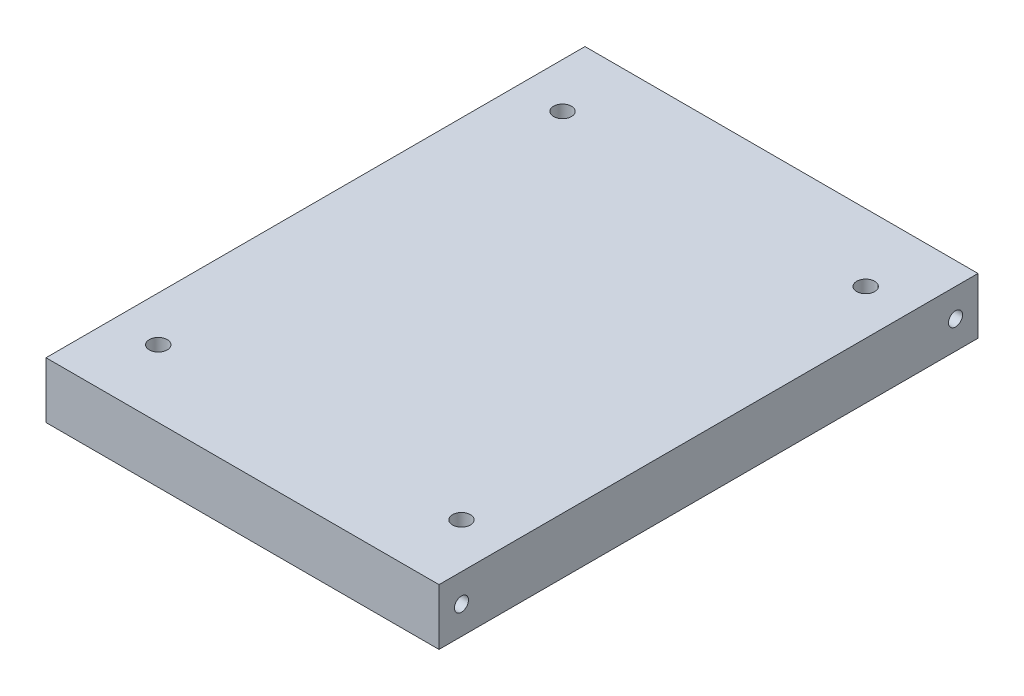
SolidWorks part; units mm, degrees
ref_plane "Front Plane" through (0, 0, 0) normal (0, 0, 1) x (1, 0, 0)
ref_plane "Top Plane" through (0, 0, 0) normal (0, 1, 0) x (1, 0, 0)
ref_plane "Right Plane" through (0, 0, 0) normal (1, 0, 0) x (0, 0, -1)
sketch "Sketch1" plane through (0, 316.5667, 0) normal (0, -1, 0) x (1, 0, 0)
  line L0 (-27, 59.5843) -> (27, -12.4157) construction
  line L2 (27, 59.5843) -> (-27, -12.4157) construction
  line L3 (-35, -24.4157) -> (35, -24.4157)
  line L4 (-35, -24.4157) -> (-35, 71.5843)
  line L5 (-35, 71.5843) -> (35, 71.5843)
  line L6 (35, -24.4157) -> (35, 71.5843)
  line L7 (-35, -24.4157) -> (35, 71.5843) construction
  line L8 (-35, 71.5843) -> (35, -24.4157) construction
  line L10 (-20.8, 71.5843) -> (20.8, 71.5843) construction
  circle A0 centre (-27, 59.5843) radius 1.6
  circle A1 centre (27, 59.5843) radius 1.6
  circle A2 centre (-27, -12.4157) radius 1.6
  circle A3 centre (27, -12.4157) radius 1.6
  point P8 (0, 23.5843)
  dimension "D1" = 3.2
  dimension "D2" = 70
extrude "Boss-Extrude1" add sketch "Sketch1" along normal blind 10
sketch "Sketch2" plane through (-35, 0, 0) normal (-1, 0, 0) x (0, 0, 1)
  line L0 (-24.4157, 311.5667) -> (71.5843, 311.5667) construction
  line L1 (-24.4157, 306.5667) -> (-24.4157, 316.5667) construction
  line L2 (71.5843, 306.5667) -> (71.5843, 316.5667) construction
  circle A0 centre (-20.4157, 311.5667) radius 1.25
  circle A1 centre (67.5843, 311.5667) radius 1.25
  dimension "D1" = 2.5
  dimension "D2" = 4
  dimension "D3" = 4
extrude "Cut-Extrude1" cut sketch "Sketch2" against normal blind 10
mirror "Mirror1" about plane through (0, 0, 0) normal (1, 0, 0) of "Cut-Extrude1"
